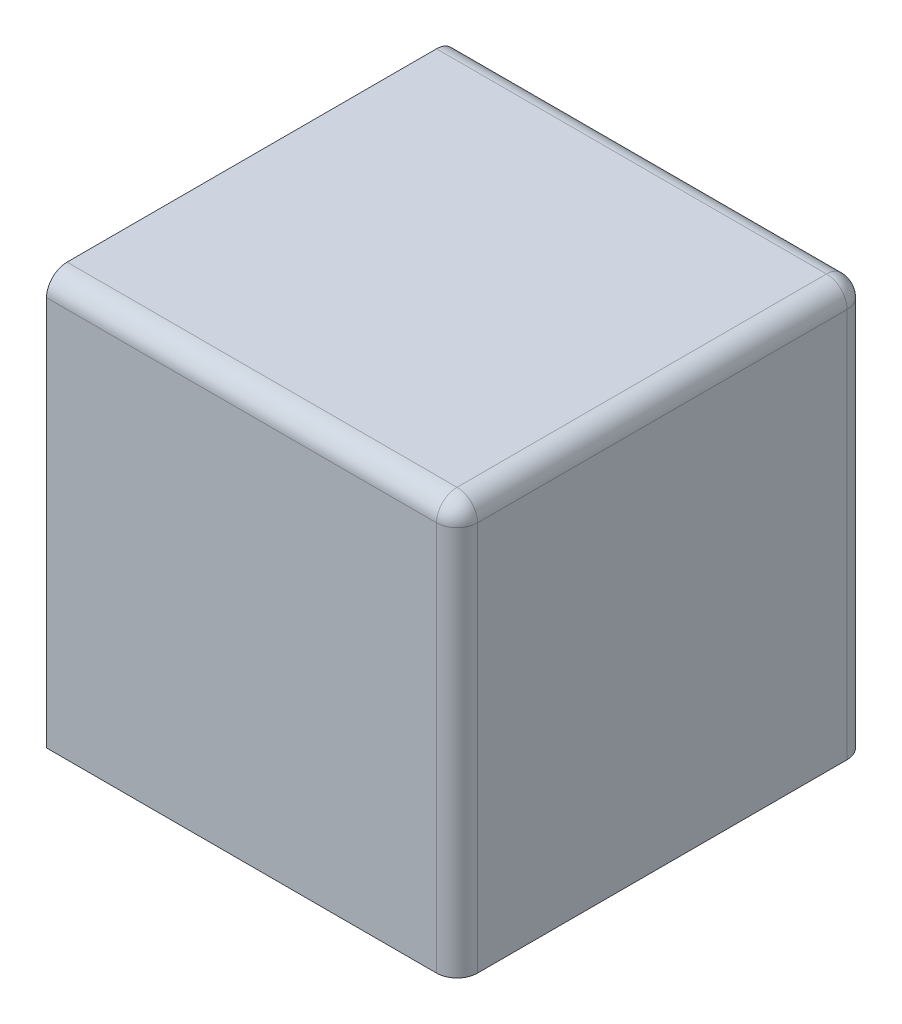
SolidWorks part; units mm, degrees
ref_plane "Front Plane" through (0, 0, 0) normal (0, 0, 1) x (1, 0, 0)
ref_plane "Top Plane" through (0, 0, 0) normal (0, 1, 0) x (1, 0, 0)
ref_plane "Right Plane" through (0, 0, 0) normal (1, 0, 0) x (0, 0, -1)
sketch "Sketch1" plane through (0, 0, 0) normal (0, 1, 0) x (1, 0, 0)
  line L1 (10, 10) -> (-10, 10)
  line L2 (10, 10) -> (10, -10)
  line L3 (10, -10) -> (-10, -10)
  line L4 (-10, 10) -> (-10, -10)
  line L5 (10, 10) -> (-10, -10) construction
  line L6 (10, -10) -> (-10, 10) construction
  point P0 (0, 0)
  dimension "D1" = 20
extrude "Boss-Extrude1" add sketch "Sketch1" along normal blind 20
sketch "Sketch2" plane through (-10, 0, 0) normal (-1, 0, 0) x (0, 0, 1)
  line L0 (-10, 20) -> (10, 20) construction
  circle A0 centre (0, 10) radius 2.05
  dimension "D1" = 4.1
  dimension "D2" = 10
extrude "Boss-Extrude2" add sketch "Sketch2" along normal blind 5
fillet "Fillet1" radius 1 5 edges at (10, 10, 10) (10, 10, -10) (0, 20, 10) (10, 20, 0) (0, 20, -10)
